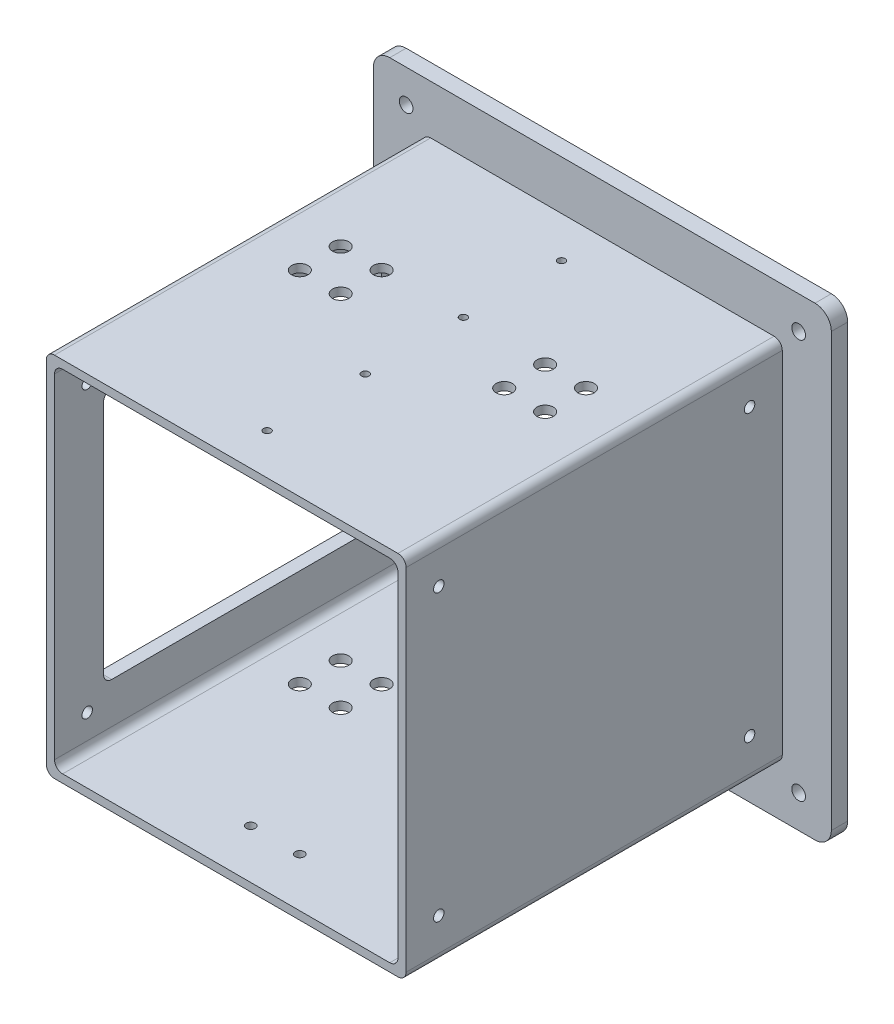
SolidWorks part; units mm, degrees
ref_plane "前视基准面" through (0, 0, 0) normal (0, 0, 1) x (1, 0, 0)
ref_plane "上视基准面" through (0, 0, 0) normal (0, 1, 0) x (1, 0, 0)
ref_plane "右视基准面" through (0, 0, 0) normal (1, 0, 0) x (0, 0, -1)
sketch "草图1" plane through (0, 0, 0) normal (0, 0, 1) x (1, 0, 0)
  line L1 (-105, -107.125) -> (105, -107.125)
  line L2 (-105, -107.125) -> (-105, 107.125)
  line L3 (-105, 107.125) -> (105, 107.125)
  line L4 (105, -107.125) -> (105, 107.125)
  line L5 (-105, -107.125) -> (105, 107.125) construction
  line L6 (-105, 107.125) -> (105, -107.125) construction
  line L7 (-110, -112.125) -> (110, -112.125)
  line L8 (-110, -112.125) -> (-110, 112.125)
  line L9 (-110, 112.125) -> (110, 112.125)
  line L10 (110, -112.125) -> (110, 112.125)
  line L11 (-110, -112.125) -> (110, 112.125) construction
  line L12 (-110, 112.125) -> (110, -112.125) construction
  point P0 (0, 0)
  point P6 (0, 0)
  dimension "D1" = 210
  dimension "D2" = 214.25
  dimension "D3" = 5
  dimension "D4" = 5
extrude "凸台-拉伸1" add sketch "草图1" along normal blind 230
sketch "草图2" plane through (0, 0, 0) normal (0, 0, -1) x (-1, 0, 0)
  line L0 (-110, 112.125) -> (110, 112.125) construction
  line L1 (-140, -142.125) -> (140, -142.125)
  line L2 (-140, -142.125) -> (-140, 142.125)
  line L3 (-140, 142.125) -> (140, 142.125)
  line L4 (140, -142.125) -> (140, 142.125)
  line L5 (-140, -142.125) -> (140, 142.125) construction
  line L6 (-140, 142.125) -> (140, -142.125) construction
  line L7 (-110, -112.125) -> (-110, 112.125) construction
  line L8 (105, 107.125) -> (105, -107.125) construction
  line L9 (105, -107.125) -> (-105, -107.125) construction
  line L10 (-105, -107.125) -> (-105, 107.125) construction
  line L11 (-105, 107.125) -> (105, 107.125) construction
  line L12 (105, 107.125) -> (105, -107.125)
  line L13 (105, -107.125) -> (-105, -107.125)
  line L14 (-105, -107.125) -> (-105, 107.125)
  line L15 (-105, 107.125) -> (105, 107.125)
  point P0 (0, 0)
  dimension "D1" = 30
  dimension "D2" = 30
extrude "凸台-拉伸2" add sketch "草图2" along normal blind 10
fillet "圆角1" radius 5 4 edges at (110, 112.125, 115) (110, -112.125, 115) (-110, -112.125, 115) (-110, 112.125, 115)
fillet "圆角2" radius 5 4 edges at (105, 107.125, 110) (-105, 107.125, 110) (105, -107.125, 110) (-105, -107.125, 110)
fillet "圆角3" radius 10 4 edges at (-140, 142.125, -5) (140, 142.125, -5) (140, -142.125, -5) (-140, -142.125, -5)
hole_wizard "Ø8.4 (8.4) 直径孔1" positions "草图3" profile "草图4" hole size "Ø8.4" standard "GB" end condition through all
sketch "草图3" plane through (0, 0, 0) normal (0, 0, 1) x (1, 0, 0)
  line L0 (130, -142.125) -> (-130, -142.125) construction
  line L1 (140, 132.125) -> (140, -132.125) construction
  line L2 (-140, -132.125) -> (-140, 132.125) construction
  line L3 (-130, 142.125) -> (130, 142.125) construction
  point P0 (120, 122.125)
  point P3 (120, -122.125)
  point P6 (-120, -122.125)
  point P10 (-120, 122.125)
  point P13 (0, 0)
  dimension "D1" = 20
  dimension "D2" = 20
  dimension "D3" = 20
  dimension "D4" = 20
  dimension "D5" = 20
  dimension "D6" = 20
  dimension "D7" = 20
  dimension "D8" = 20
sketch "草图4" plane through (120, 122.125, 0) normal (1, 0, 0) x (0, -1, 0)
  line L0 (0, 0) -> (0, 10)
  line L1 (0, 10) -> (4.2, 10)
  line L2 (4.2, 10) -> (4.2, 0)
  line L5 (4.2, 0) -> (0, 0)
  line L11 (0, -6.35) -> (0, 107.95) construction
  dimension "通孔孔直径" = 8.4
  dimension "通孔孔深度" = 10
sketch "草图18" plane through (0, 112.125, 0) normal (0, 1, 0) x (1, 0, 0)
  line L0 (105, -230) -> (-105, -230) construction
  line L1 (-105, 0) -> (-105, -230) construction
  line L2 (105, -230) -> (105, 0) construction
  point P0 (-75, -85)
  point P1 (-75, -110)
  point P2 (-50, -110)
  point P3 (-50, -85)
  point P5 (50, -110)
  point P6 (75, -110)
  point P8 (75, -85)
  point P16 (50, -85)
  dimension "D1" = 25
  dimension "D2" = 25
  dimension "D3" = 35.3553
  dimension "D4" = 25
  dimension "D5" = 35.3553
  dimension "D6" = 25
  dimension "D7" = 30
  dimension "D8" = 30
  dimension "D9" = 25
  dimension "D10" = 25
  dimension "D11" = 25
  dimension "D12" = 25
  dimension "D13" = 120
  dimension "D14" = 120
  dimension "D15" = 35.3553
  dimension "D16" = 55
hole_wizard "大小mm 暗销孔11" positions "草图33" profile "草图34" hole size "Ø10.0" standard "GB" end condition through all
sketch "草图33" plane through (0, 112.125, 0) normal (0, 1, 0) x (1, 0, 0)
  point P0 (-75, -85)
  point P3 (-50, -85)
  point P6 (-50, -110)
  point P9 (-75, -110)
  point P12 (50, -110)
  point P15 (50, -85)
  point P18 (75, -85)
  point P21 (75, -110)
sketch "草图34" plane through (-75, 112.125, 85) normal (1, 0, 0) x (0, 0, 1)
  line L0 (0, 0) -> (0, 254.25)
  line L1 (0, 254.25) -> (5, 254.25)
  line L2 (5, 254.25) -> (5, 0)
  line L5 (5, 0) -> (0, 0)
  line L11 (0, -6.35) -> (0, 107.95) construction
  dimension "通孔孔直径" = 10
  dimension "通孔孔深度" = 254.25
sketch "草图35" plane through (0, -112.125, 0) normal (0, -1, 0) x (1, 0, 0)
  line L0 (130, 0) -> (-130, 0) construction
  line L2 (-105, 0) -> (105, 0) construction
  line L3 (105, 0) -> (105, 230) construction
  line L4 (-105, 230) -> (-105, 0) construction
  point P0 (15, 200)
  point P1 (19, 25.5)
  point P2 (-19, 25.5)
  point P4 (-15, 200)
  dimension "D1" = 90
  dimension "D2" = 38
  dimension "D4" = 19
  dimension "D5" = 200
  dimension "D6" = 200
  dimension "D7" = 25.5
  dimension "D8" = 25.5
  dimension "D9" = 90
sketch "草图38" plane through (0, 112.125, 0) normal (0, 1, 0) x (1, 0, 0)
  line L0 (-105, 0) -> (-105, -230) construction
  line L2 (105, 0) -> (-105, 0) construction
  point P0 (0, -25)
  point P1 (0, -85)
  point P2 (0, -205)
  point P3 (0, -145)
  dimension "D1" = 105
  dimension "D2" = 60
  dimension "D3" = 60
  dimension "D4" = 60
  dimension "D5" = 25
  dimension "D6" = 105
  dimension "D7" = 105
  dimension "D8" = 105
hole_wizard "Ø4.5 (4.5) 直径孔1" positions "草图39" profile "草图40" hole size "Ø4.5" standard "GB" end condition up to next
sketch "草图39" plane through (0, 112.125, 0) normal (0, 1, 0) x (1, 0, 0)
  point P0 (0, -25)
  point P3 (0, -85)
  point P6 (0, -145)
  point P9 (0, -205)
sketch "草图40" plane through (0, 112.125, 25) normal (1, 0, 0) x (0, 0, 1)
  line L0 (0, 0) -> (0, 5)
  line L1 (0, 5) -> (2.25, 5)
  line L2 (2.25, 5) -> (2.25, 0)
  line L5 (2.25, 0) -> (0, 0)
  line L11 (0, -6.35) -> (0, 107.95) construction
  dimension "通孔孔直径" = 4.5
  dimension "通孔孔深度" = 5
hole_wizard "Ø6.6 (6.6) 直径孔1" positions "草图41" profile "草图42" hole size "Ø6.6" standard "GB" end condition up to next
sketch "草图41" plane through (0, -112.125, 0) normal (0, -1, 0) x (-1, 0, 0)
  point P0 (19, -25.5)
  point P3 (-19, -25.5)
sketch "草图42" plane through (-19, -112.125, 25.5) normal (1, 0, 0) x (0, 0, -1)
  line L0 (0, 0) -> (0, 5)
  line L1 (0, 5) -> (3.3, 5)
  line L2 (3.3, 5) -> (3.3, 0)
  line L5 (3.3, 0) -> (0, 0)
  line L11 (0, -6.35) -> (0, 107.95) construction
  dimension "通孔孔直径" = 6.6
  dimension "通孔孔深度" = 5
hole_wizard "Ø5.5 (5.5) 直径孔1" positions "草图43" profile "草图44" hole size "Ø5.5" standard "GB" end condition up to next
sketch "草图43" plane through (0, -112.125, 0) normal (0, -1, 0) x (-1, 0, 0)
  point P0 (15, -200)
  point P3 (-15, -200)
sketch "草图44" plane through (-15, -112.125, 200) normal (1, 0, 0) x (0, 0, -1)
  line L0 (0, 0) -> (0, 5)
  line L1 (0, 5) -> (2.75, 5)
  line L2 (2.75, 5) -> (2.75, 0)
  line L5 (2.75, 0) -> (0, 0)
  line L11 (0, -6.35) -> (0, 107.95) construction
  dimension "通孔孔直径" = 5.5
  dimension "通孔孔深度" = 5
sketch "草图45" plane through (-110, 0, 0) normal (-1, 0, 0) x (0, 0, 1)
  line L0 (230, 107.125) -> (0, 107.125) construction
  line L1 (200, -77.125) -> (30, -77.125)
  line L2 (200, -77.125) -> (200, 77.125)
  line L3 (200, 77.125) -> (30, 77.125)
  line L4 (30, -77.125) -> (30, 77.125)
  line L5 (200, -77.125) -> (30, 77.125) construction
  line L6 (200, 77.125) -> (30, -77.125) construction
  line L7 (0, -107.125) -> (230, -107.125) construction
  line L8 (0, -132.125) -> (0, 132.125) construction
  line L9 (230, 107.125) -> (230, -107.125) construction
  point P0 (115, 0)
  dimension "D1" = 30
  dimension "D2" = 30
  dimension "D3" = 30
  dimension "D4" = 30
extrude "切除-拉伸1" cut sketch "草图45" against normal up to next
fillet "圆角4" radius 5 4 edges at (-107.5, -77.125, 30) (-107.5, -77.125, 200) (-107.5, 77.125, 200) (-107.5, 77.125, 30)
sketch "草图46" plane through (110, 0, 0) normal (1, 0, 0) x (0, 0, -1)
  line L0 (-195, 77.125) -> (-35, 77.125) construction
  line L1 (-200, -72.125) -> (-200, 72.125) construction
  line L2 (-30, 72.125) -> (-30, -72.125) construction
  line L3 (-35, -77.125) -> (-195, -77.125) construction
  point P0 (-210, 87.125)
  point P1 (-210, -87.125)
  point P2 (-20, -87.125)
  point P3 (-20, 87.125)
  dimension "D1" = 10
  dimension "D2" = 10
  dimension "D3" = 10
  dimension "D4" = 10
  dimension "D5" = 10
  dimension "D6" = 10
  dimension "D7" = 10
  dimension "D8" = 10
hole_wizard "Ø6.4 (6.4) 直径孔1" positions "草图47" profile "草图48" hole size "Ø6.4" standard "GB" end condition through all
sketch "草图47" plane through (110, 0, 0) normal (1, 0, 0) x (0, 0, -1)
  point P0 (-210, 87.125)
  point P3 (-20, 87.125)
  point P6 (-20, -87.125)
  point P9 (-210, -87.125)
sketch "草图48" plane through (110, 87.125, 210) normal (0, 1, 0) x (0, 0, -1)
  line L0 (0, 0) -> (0, 250)
  line L1 (0, 250) -> (3.2, 250)
  line L2 (3.2, 250) -> (3.2, 0)
  line L5 (3.2, 0) -> (0, 0)
  line L11 (0, -6.35) -> (0, 107.95) construction
  dimension "通孔孔直径" = 6.4
  dimension "通孔孔深度" = 250
sketch "草图49" plane through (-110, 0, 0) normal (-1, 0, 0) x (0, 0, 1)
  line L0 (195, 77.125) -> (35, 77.125) construction
  line L1 (27, 80.125) -> (203, 80.125)
  line L2 (27, 80.125) -> (27, -80.125)
  line L3 (27, -80.125) -> (203, -80.125)
  line L4 (203, 80.125) -> (203, -80.125)
  line L5 (35, -77.125) -> (195, -77.125) construction
  line L6 (30, 72.125) -> (30, -72.125) construction
  line L7 (200, -72.125) -> (200, 72.125) construction
  line L8 (200, -72.125) -> (200, 72.125)
  line L9 (35, -77.125) -> (195, -77.125)
  line L10 (30, 72.125) -> (30, -72.125)
  line L11 (195, 77.125) -> (35, 77.125)
  arc A0 (200, 72.125) -> (195, 77.125) centre (195, 72.125) ccw construction
  arc A1 (195, -77.125) -> (200, -72.125) centre (195, -72.125) ccw construction
  arc A2 (30, -72.125) -> (35, -77.125) centre (35, -72.125) ccw construction
  arc A3 (35, 77.125) -> (30, 72.125) centre (35, 72.125) ccw construction
  arc A4 (200, 72.125) -> (195, 77.125) centre (195, 72.125) ccw
  arc A5 (195, -77.125) -> (200, -72.125) centre (195, -72.125) ccw
  arc A6 (30, -72.125) -> (35, -77.125) centre (35, -72.125) ccw
  arc A7 (35, 77.125) -> (30, 72.125) centre (35, 72.125) ccw
  dimension "D1" = 3
  dimension "D2" = 3
  dimension "D3" = 3
  dimension "D4" = 3
extrude "凸台-拉伸3" add sketch "草图49" along normal blind 3
fillet "圆角5" radius 5 4 edges at (-111.5, 80.125, 27) (-111.5, -80.125, 27) (-111.5, -80.125, 203) (-111.5, 80.125, 203)
sketch "草图50" plane through (0, 0, -10) normal (0, 0, -1) x (-1, 0, 0)
  line L0 (100, 107.125) -> (-100, 107.125) construction
  line L1 (108, -110.125) -> (-108, -110.125)
  line L2 (108, -110.125) -> (108, 110.125)
  line L3 (108, 110.125) -> (-108, 110.125)
  line L4 (-108, -110.125) -> (-108, 110.125)
  line L5 (108, -110.125) -> (-108, 110.125) construction
  line L6 (108, 110.125) -> (-108, -110.125) construction
  line L7 (-105, 102.125) -> (-105, -102.125) construction
  line L8 (-100, -107.125) -> (100, -107.125) construction
  line L9 (105, -102.125) -> (105, 102.125) construction
  line L10 (-100, -107.125) -> (100, -107.125)
  line L11 (105, -102.125) -> (105, 102.125)
  line L12 (100, 107.125) -> (-100, 107.125)
  line L13 (-105, 102.125) -> (-105, -102.125)
  arc A0 (-105, -102.125) -> (-100, -107.125) centre (-100, -102.125) ccw construction
  arc A1 (100, -107.125) -> (105, -102.125) centre (100, -102.125) ccw construction
  arc A2 (105, 102.125) -> (100, 107.125) centre (100, 102.125) ccw construction
  arc A3 (-100, 107.125) -> (-105, 102.125) centre (-100, 102.125) ccw construction
  arc A4 (-105, -102.125) -> (-100, -107.125) centre (-100, -102.125) ccw
  arc A5 (100, -107.125) -> (105, -102.125) centre (100, -102.125) ccw
  arc A6 (105, 102.125) -> (100, 107.125) centre (100, 102.125) ccw
  arc A7 (-100, 107.125) -> (-105, 102.125) centre (-100, 102.125) ccw
  point P0 (0, 0)
  dimension "D1" = 3
  dimension "D2" = 3
extrude "凸台-拉伸4" add sketch "草图50" along normal blind 3
fillet "圆角6" radius 5 4 edges at (-108, 110.125, -11.5) (-108, -110.125, -11.5) (108, -110.125, -11.5) (108, 110.125, -11.5)
